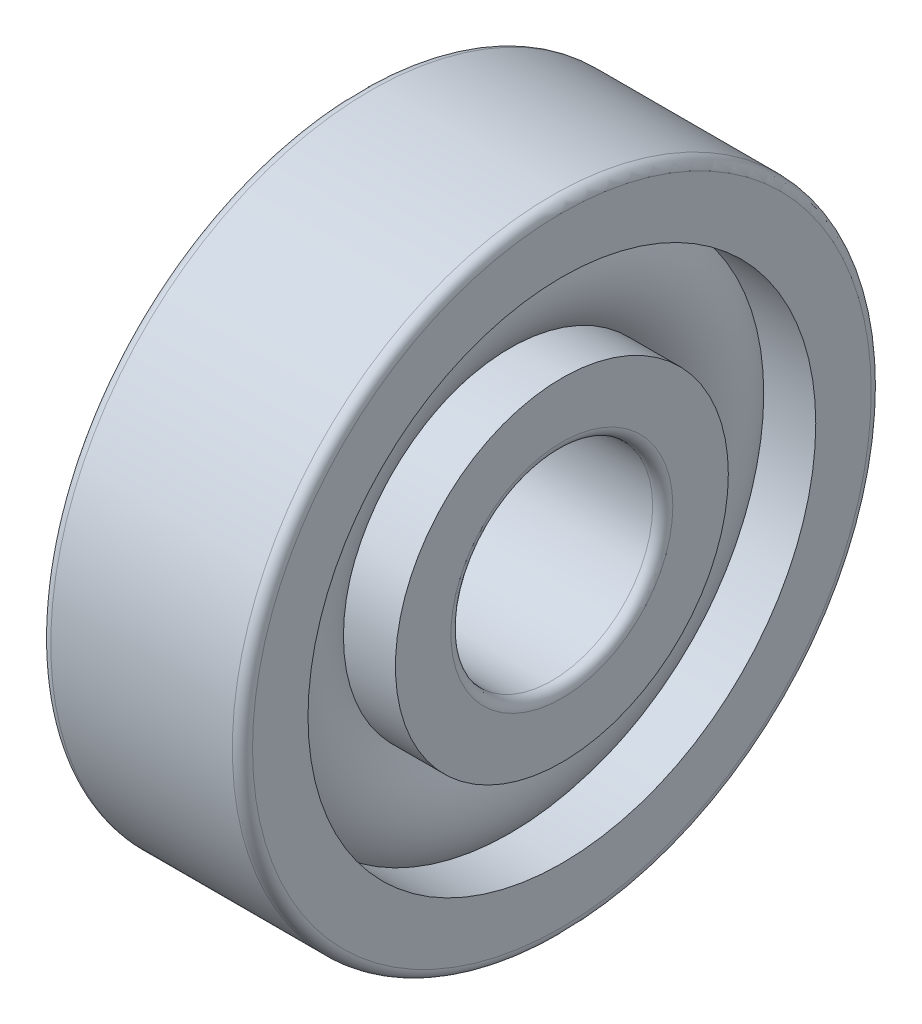
SolidWorks part; units mm, degrees
ref_plane "Plane1" through (0, 0, 0) normal (0, 0, 1) x (1, 0, 0)
ref_plane "Plane2" through (0, 0, 0) normal (0, 1, 0) x (1, 0, 0)
ref_plane "Plane3" through (0, 0, 0) normal (1, 0, 0) x (0, 0, -1)
sketch "Clipboard" plane through (0, 0, 0) normal (0, 0, 1) x (1, 0, 0)
  line L0 (-10, 0) -> (10, 0) construction
  line L1 (0, 0) -> (22.3471, -0.7804)
  line L2 (0, 0) -> (6.2462, 0.2181)
  line L3 (0, 0) -> (22.3471, -0.7804)
  line L4 (0, 0) -> (-22.3573, -0.3902)
  dimension "BallCLRad" = 6.25
sketch "CagSpiSke" plane through (0, 0, 0) normal (0, 0, 1) x (1, 0, 0)
  line L0 (0.195, 5.925) -> (0.195, 6.575)
  line L1 (0.195, 6.575) -> (-0.195, 6.575)
  line L2 (-0.195, 6.575) -> (-0.195, 5.925)
  line L3 (-0.195, 5.925) -> (0.195, 5.925)
  line L4 (-20.6375, 0) -> (20.6375, 0) construction
  line L5 (0, 0) -> (0, 23.7692) construction
  dimension "OD" = 13.15
  dimension "ID" = 11.85
revolve "CageSpine" add sketch "CagSpiSke" angle 0.001 about L4 reverse direction yes
ref_axis "Axis1" through (-50, 0, 0) along (1, 0, 0)
sketch "CagBalSke" plane through (0, 0, 0) normal (0, 0, 1) x (1, 0, 0)
  line L0 (-2.145, 6.25) -> (2.145, 6.25)
  line L1 (-1.905, 6.25) -> (1.905, 6.25) construction
  line L2 (-10, 0) -> (10, 0) construction
  line L3 (0, 0) -> (0, 24) construction
  arc A0 (2.145, 6.25) -> (-2.145, 6.25) centre (0, 6.25) cw
  dimension "BallCLRad" = 6.25
revolve "CageBall" [suppressed] add sketch "CagBalSke" angle 360 about L1 reverse direction yes
pattern_circular "CageBalls" [suppressed] count 2 every 180 about axis through (-50, 0, 0) along (1, 0, 0)
sketch "CagTrmODSke" plane through (0, 0, 0) normal (0, 0, 1) x (1, 0, 0)
  line L0 (2.146, 6.575) -> (2.146, 8.396)
  line L1 (2.146, 8.396) -> (-2.146, 8.396)
  line L2 (-2.146, 8.396) -> (-2.146, 6.575)
  line L3 (-2.146, 6.575) -> (2.146, 6.575)
  line L4 (-20.6375, 0) -> (20.6375, 0) construction
  line L5 (0, 0) -> (0, 25) construction
  dimension "Width" = 4.292
  dimension "ID" = 13.15
  dimension "OD" = 16.792
revolve "CageTrimOD" [suppressed] cut sketch "CagTrmODSke" angle 360 about L4 reverse direction yes
sketch "CagTrmIDSke" plane through (0, 0, 0) normal (0, 0, 1) x (1, 0, 0)
  line L0 (2.146, 4.106) -> (2.146, 5.925)
  line L1 (2.146, 5.925) -> (-2.146, 5.925)
  line L2 (-2.146, 5.925) -> (-2.146, 4.106)
  line L3 (-2.146, 4.106) -> (2.146, 4.106)
  line L4 (-20.6375, 0) -> (20.6375, 0) construction
  line L5 (0, 0) -> (0, 25) construction
  dimension "Width" = 4.292
  dimension "ID" = 8.212
  dimension "OD" = 11.85
revolve "CageTrimID" [suppressed] cut sketch "CagTrmIDSke" angle 360 about L4 reverse direction yes
sketch "BalSimSke" plane through (0, 0, 0) normal (0, 0, 1) x (1, 0, 0)
  line L0 (-10, 0) -> (10, 0) construction
  line L1 (-10, 6.25) -> (10, 6.25) construction
  line L2 (0, 0) -> (0, 23) construction
  circle A0 centre (0, 6.25) radius 1.95
  dimension "BallCLRad" = 6.25
  dimension "Ball_diameter" = 3.9
revolve "BallsSimplified" add sketch "BalSimSke" angle 360 about L0
sketch "BalDetSke" plane through (0, 0, 0) normal (0, 0, 1) x (1, 0, 0)
  line L0 (-1.95, 6.25) -> (1.95, 6.25)
  line L1 (-1.905, 6.25) -> (1.905, 6.25) construction
  line L2 (0, 0) -> (0, 25) construction
  arc A0 (1.95, 6.25) -> (-1.95, 6.25) centre (0, 6.25) cw
  dimension "BallCLRad" = 6.25
  dimension "Ball_diameter" = 3.9
revolve "BallDetailed" [suppressed] add sketch "BalDetSke" angle 360 about L1 reverse direction yes
sketch "InnRacSke" plane through (0, 0, 0) normal (0, 0, 1) x (1, 0, 0)
  line L0 (-1.4197, 4.95) -> (-3, 4.95)
  line L1 (-3, 4.95) -> (-3, 3.3)
  line L2 (-2.7, 3) -> (2.7, 3)
  line L3 (3, 3.3) -> (3, 4.95)
  line L4 (3, 4.95) -> (1.4197, 4.95)
  line L5 (-20.6375, 0) -> (20.6375, 0) construction
  line L6 (0, 0) -> (0, 30) construction
  arc A0 (-3, 3.3) -> (-2.7, 3) centre (-2.7, 3.3) ccw
  arc A1 (2.7, 3) -> (3, 3.3) centre (2.7, 3.3) ccw
  arc A2 (1.4197, 4.95) -> (-1.4197, 4.95) centre (0, 6.25) cw
  dimension "BallCLRad" = 6.25
  dimension "Fillet_radius" = 0.3
  dimension "Ball_diameter" = 3.85
  dimension "ID" = 6
  dimension "OD" = 9.9
  dimension "Width" = 6
revolve "InnerRace" add sketch "InnRacSke" angle 360 about L5 reverse direction yes
sketch "OutRacSke" plane through (0, 0, 0) normal (0, 0, 1) x (1, 0, 0)
  line L0 (-1.4197, 7.55) -> (-3, 7.55)
  line L1 (-3, 7.55) -> (-3, 9.2)
  line L2 (-2.7, 9.5) -> (2.7, 9.5)
  line L3 (3, 9.2) -> (3, 7.55)
  line L4 (3, 7.55) -> (1.4197, 7.55)
  line L5 (-20.6375, 0) -> (20.6375, 0) construction
  line L6 (0, 0) -> (0, 30) construction
  arc A0 (-3, 9.2) -> (-2.7, 9.5) centre (-2.7, 9.2) cw
  arc A1 (2.7, 9.5) -> (3, 9.2) centre (2.7, 9.2) cw
  arc A2 (1.4197, 7.55) -> (-1.4197, 7.55) centre (0, 6.25) ccw
  dimension "BallCLRad" = 6.25
  dimension "Fillet_radius" = 0.3
  dimension "Ball_diameter" = 3.85
  dimension "Width" = 6
revolve "OuterRace" add sketch "OutRacSke" angle 360 about L5 reverse direction yes
pattern_circular "BallsDetailed" [suppressed] count 2 every 180 about axis through (-50, 0, 0) along (1, 0, 0)
equation "\"BallCLRad@Clipboard\" = ( \"OD@OutRacSke\" + \"ID@InnRacSke\" ) / 4"
equation "\"BallCLRad@BalSimSke\" = \"BallCLRad@Clipboard\""
equation "\"BallCLRad@BalDetSke\" = \"BallCLRad@Clipboard\""
equation "\"BallCLRad@InnRacSke\" = \"BallCLRad@Clipboard\""
equation "\"BallCLRad@OutRacSke\" = \"BallCLRad@Clipboard\""
equation "\"Ball_diameter@InnRacSke\" = \"Ball_diameter@BalDetSke\" - 0.05"
equation "\"Ball_diameter@OutRacSke\" = \"Ball_diameter@BalDetSke\" - 0.05"
equation "\"Ball_diameter@BalSimSke\" = \"Ball_diameter@BalDetSke\""
equation "\"Width@OutRacSke\" = \"Width@InnRacSke\""
equation "\"Fillet_radius@OutRacSke\" = \"Fillet_radius@InnRacSke\""
equation "\"Max_count@Clipboard\" = int( 3.14159265 / atn(( \"Ball_diameter@BalDetSke\" / 2) / sqr( \"BallCLRad@Clipboard\"  *  \"BallCLRad@Clipboard\" - ( \"Ball_diameter@BalDetSke\" / 2) *  ( \"Ball_diameter@BalDetSke\" / 2))))"
equation "\"Max_count@Clipboard\" = ((sgn( \"Max_count@Clipboard\" - \"Count@Clipboard\" )-1)*( \"Max_count@Clipboard\" - \"Count@Clipboard\" ))/-2+ \"Count@Clipboard\""
equation "\"Count@BallsDetailed\" = int( \"Show_count@Clipboard\" ) "
equation "\"Count@BallsDetailed\" = ((sgn( \"Count@BallsDetailed\" - \"Max_count@Clipboard\" )-1)*( \"Count@BallsDetailed\" - \"Max_count@Clipboard\" ))/-2+ \"Max_count@Clipboard\""
equation "\"Count@BallsDetailed\" = ((sgn( \"Count@BallsDetailed\" - \"Min_count@Clipboard\" )+1)*( \"Count@BallsDetailed\" - \"Min_count@Clipboard\"))/2 +\"Min_count@Clipboard\""
equation "\"Angle@BallsDetailed\" = 360.0 / \"Max_count@Clipboard\""
equation "\"BallCLRad@CagBalSke\" = \"BallCLRad@Clipboard\""
equation "\"Count@CageBalls\" = \"Count@BallsDetailed\""
equation "\"Angle@CageBalls\" = \"Angle@BallsDetailed\""
equation "\"Angle@CageSpine\" =  \"Angle@CageBalls\" * ( \"Count@CageBalls\" -1 + int( \"Count@CageBalls\" / \"Max_count@Clipboard\" ) )  + 0.001 -  int( \"Count@CageBalls\" / \"Max_count@Clipboard\" ) * 0.001"
equation "\"Angle@CageSpine\" =  \"Angle@CageSpine\" * int( \"Min_count@Clipboard\" / 2) + int(1 / \"Min_count@Clipboard\")  * 0.001"
equation "\"CageWallOD@CagBalSke\" =  \"Ball_diameter@BalDetSke\" * 1.1"
equation "\"Thickness@CagSpiSke\" =  \"Ball_diameter@BalDetSke\" * 0.1"
equation "\"OD@CagTrmODSke\" = \"BallCLRad@Clipboard\" * 2 + \"CageWallOD@CagBalSke\" + 0.002"
equation "\"ID@CagTrmODSke\" = \"BallCLRad@Clipboard\" * 2 + \"Ball_diameter@BalDetSke\" / 6"
equation "\"OD@CagTrmIDSke\" = \"BallCLRad@Clipboard\" * 2 - \"Ball_diameter@BalDetSke\" / 6"
equation "\"ID@CagTrmIDSke\" = \"BallCLRad@Clipboard\" * 2 - \"CageWallOD@CagBalSke\" + 0.002"
equation "\"OD@CagSpiSke\" = \"ID@CagTrmODSke\""
equation "\"ID@CagSpiSke\" = \"OD@CagTrmIDSke\""
equation "\"Width@CagTrmODSke\" = \"CageWallOD@CagBalSke\" + 0.002"
equation "\"Width@CagTrmIDSke\" = \"CageWallOD@CagBalSke\" + 0.002"
